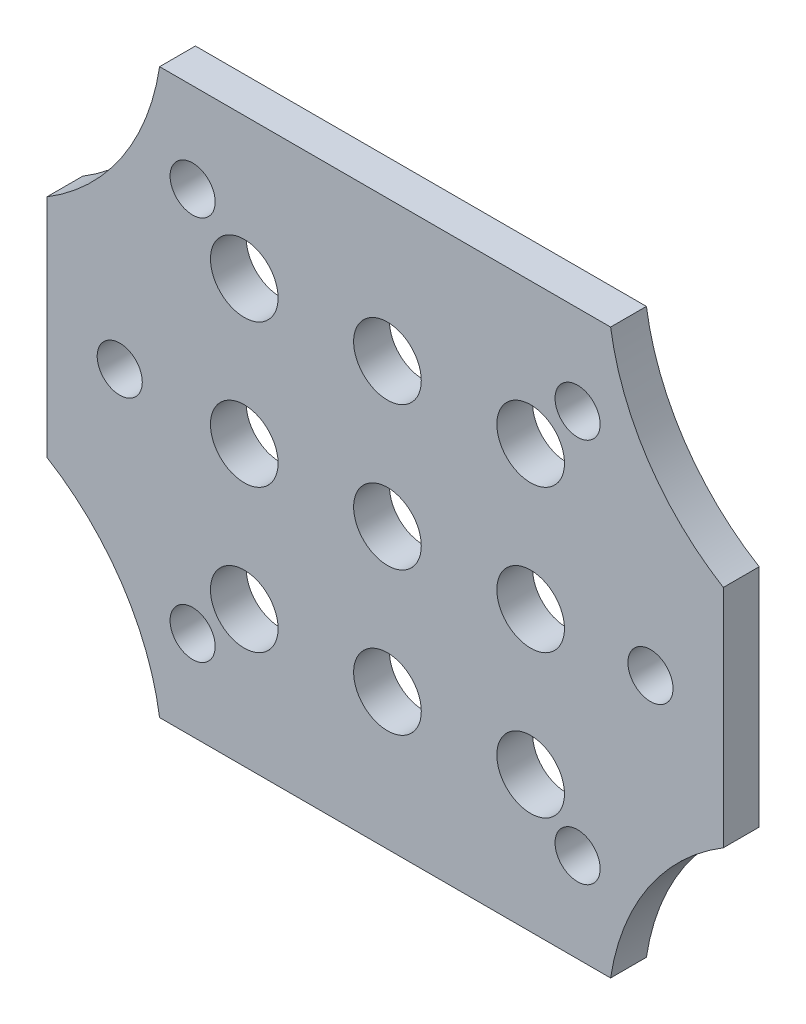
SolidWorks part; units mm, degrees
material "Custom Plastic"
ref_plane "X-Y Datum" through (0, 0, 0) normal (0, 0, 1) x (1, 0, 0)
ref_plane "X-Z Datum" through (0, 0, 0) normal (0, 1, 0) x (1, 0, 0)
ref_plane "Y-Z Datum" through (0, 0, 0) normal (1, 0, 0) x (0, 0, -1)
sketch "Sketch1" plane through (0, 0, 0) normal (0, 0, 1) x (1, 0, 0)
  line L1 (-30, -25) -> (30, -25)
  line L2 (-30, -25) -> (-30, 25)
  line L3 (-30, 25) -> (30, 25)
  line L4 (30, -25) -> (30, 25)
  line L5 (-30, -25) -> (30, 25) construction
  line L6 (-30, 25) -> (30, -25) construction
  point P0 (0, 0)
  dimension "D1" = 60
  dimension "D2" = 50
extrude "Boss-Extrude1" add sketch "Sketch1" along normal blind 3.175
sketch "Sketch2" plane through (0, 0, 3.175) normal (0, 0, 1) x (1, 0, 0)
  line L0 (-30, 0) -> (-17.0711, 0) construction
  line L1 (-17.0711, -17.0711) -> (17.0711, -17.0711) construction
  line L2 (-17.0711, -17.0711) -> (-17.0711, 17.0711) construction
  line L3 (-17.0711, 17.0711) -> (17.0711, 17.0711) construction
  line L4 (17.0711, -17.0711) -> (17.0711, 17.0711) construction
  line L5 (-17.0711, -17.0711) -> (17.0711, 17.0711) construction
  line L6 (-17.0711, 17.0711) -> (17.0711, -17.0711) construction
  line L7 (-30, 25) -> (-30, -25) construction
  line L8 (17.0711, 0) -> (30, 0) construction
  line L9 (30, -25) -> (30, 25) construction
  line L10 (-30, 0) -> (-30, 10) construction
  line L11 (0, 17.0711) -> (0, 25) construction
  line L12 (30, 25) -> (-30, 25) construction
  line L13 (0, 25) -> (-20, 25) construction
  line L15 (0, -43.0151) -> (0, 43.0151) construction
  line L16 (55.1739, 0) -> (-55.1739, 0) construction
  circle A0 centre (-17.0711, 17.0711) radius 2
  circle A1 centre (17.0711, 17.0711) radius 2
  circle A2 centre (-17.0711, -17.0711) radius 2
  circle A3 centre (17.0711, -17.0711) radius 2
  circle A4 centre (-23.5355, 0) radius 2
  circle A5 centre (23.5355, 0) radius 2
  arc A6 (-30, 10) -> (-20, 25) centre (-41.0638, 28.2092) ccw
  arc A7 (30, 10) -> (20, 25) centre (41.0638, 28.2092) cw
  arc A8 (-30, -10) -> (-20, -25) centre (-41.0638, -28.2092) cw
  arc A9 (30, -10) -> (20, -25) centre (41.0638, -28.2092) ccw
  point P0 (0, 0)
  line M3 (30, -25) -> (30, 25)
  line M4 (30, 25) -> (-30, 25)
  line M5 (-30, 25) -> (-30, -25)
  line M6 (-30, -25) -> (30, -25)
  dimension "D1" = 4
  dimension "D2" = 4
  dimension "D3" = 10
  dimension "D4" = 20
extrude "Cut-Extrude1" cut sketch "Sketch2" against normal blind 6.35 contours A6 M5 M4 | A8 M5 M6 | A9 M3 M6 | A7 M3 M4 | A1 | A5 | A3 | A2 | A4 | A0 region at (-17.0711, 17.0711, 3.175) region at (17.0711, 17.0711, 3.175) region at (-17.0711, -17.0711, 3.175) region at (17.0711, -17.0711, 3.175) region at (-23.5355, 0, 3.175) region at (23.5355, 0, 3.175) region at (-26.0956, 19.2796, 3.175) region at (-26.0956, -19.2796, 3.175) region at (26.0956, 19.2796, 3.175) region at (26.0956, -19.2796, 3.175)
sketch "Sketch3" plane through (0, 0, 3.175) normal (0, 0, 1) x (1, 0, 0)
  line L0 (-17.0711, 17.0711) -> (17.0711, -17.0711) construction
  circle A0 centre (-12.4909, 12.4909) radius 3
extrude "Cut-Extrude2" cut sketch "Sketch3" against normal through all
pattern_linear "LPattern1" count 3 spacing 12.7 along (1, 0, 0) of "Cut-Extrude2"
pattern_linear "LPattern2" count 3 spacing 12.7 along (0, -1, 0) of "LPattern1"
